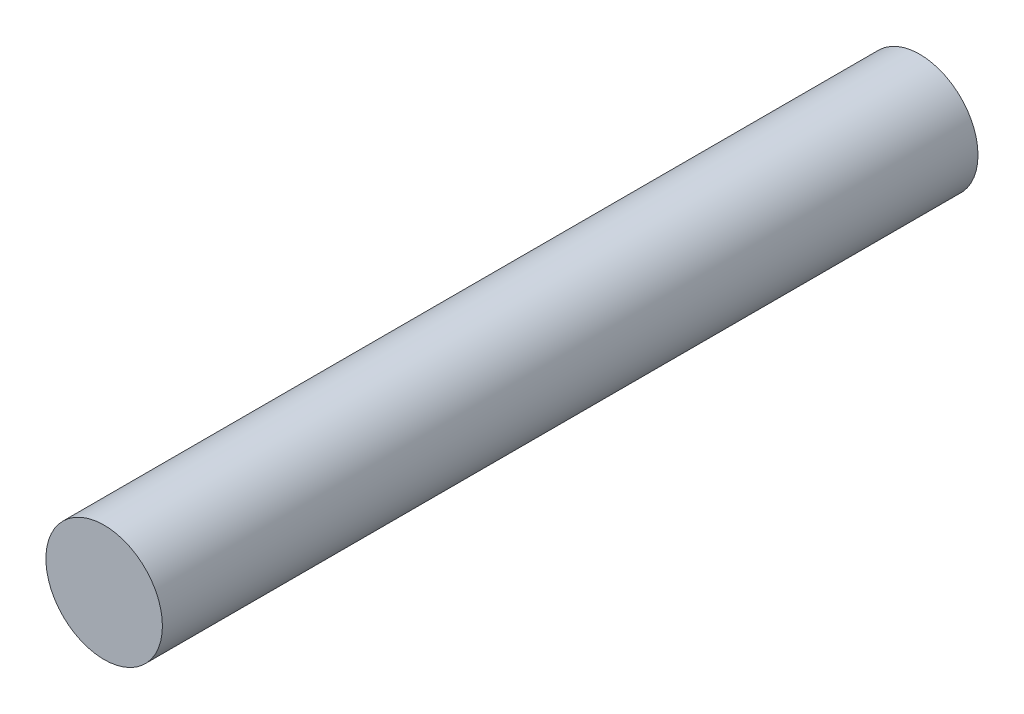
SolidWorks part; units mm, degrees
material "6061-T6 (SS)"
ref_plane "Front" through (0, 0, 0) normal (0, 0, 1) x (1, 0, 0)
ref_plane "Top" through (0, 0, 0) normal (0, 1, 0) x (1, 0, 0)
ref_plane "Right" through (0, 0, 0) normal (1, 0, 0) x (0, 0, -1)
sketch "Sketch1" plane through (0, 0, 0) normal (0, 0, 1) x (1, 0, 0)
  circle A0 centre (0, 0) radius 3.175
  dimension "D1" = 6.35
extrude "Boss-Extrude1" add sketch "Sketch1" along normal blind 44.45
